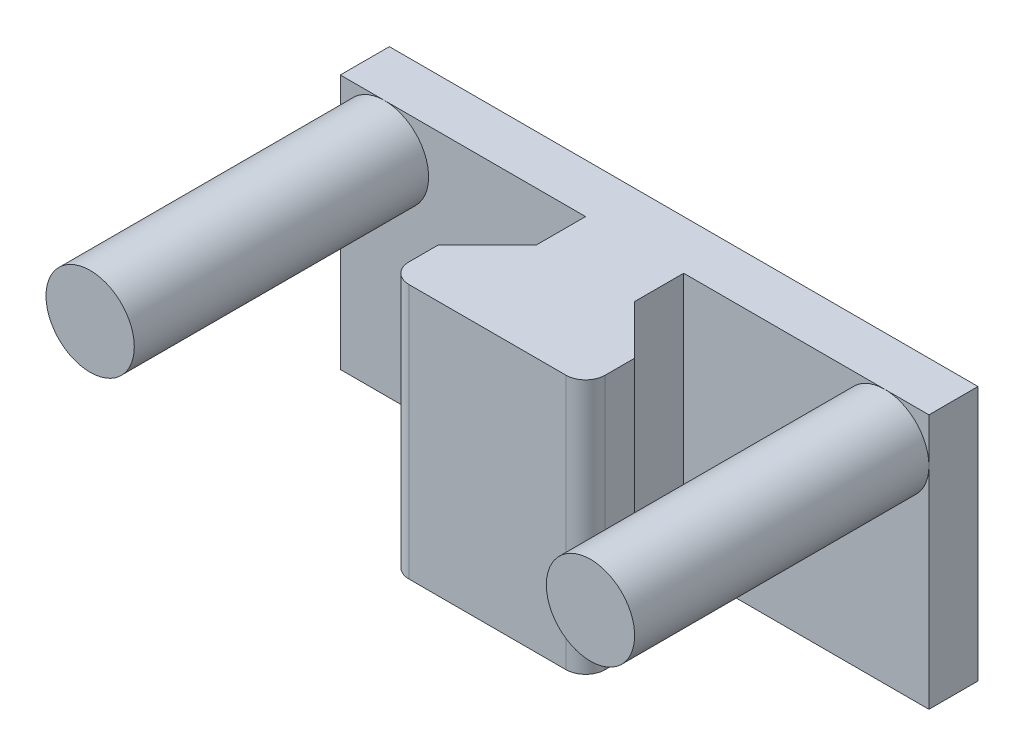
SolidWorks part; units mm, degrees
ref_plane "Front Plane" through (0, 0, 0) normal (0, 0, 1) x (1, 0, 0)
ref_plane "Top Plane" through (0, 0, 0) normal (0, 1, 0) x (1, 0, 0)
ref_plane "Right Plane" through (0, 0, 0) normal (1, 0, 0) x (0, 0, -1)
sketch "Sketch1" plane through (0, 0, 0) normal (0, 1, 0) x (1, 0, 0)
  line L0 (10, 0) -> (-10, 0)
  line L1 (-10, 0) -> (-10, 5)
  line L2 (-10, 5) -> (-5, 5)
  line L3 (-5, 5) -> (-5, 15)
  line L4 (-5, 15) -> (-30, 15)
  line L5 (-30, 15) -> (-30, 20)
  line L6 (-30, 20) -> (30, 20)
  line L7 (0, 20) -> (0, 0)
  line L8 (30, 15) -> (30, 20)
  line L9 (5, 15) -> (30, 15)
  line L10 (5, 5) -> (5, 15)
  line L11 (10, 5) -> (5, 5)
  line L12 (10, 0) -> (10, 5)
  dimension "D1" = 10
  dimension "D2" = 5
  dimension "D3" = 10
  dimension "D4" = 30
  dimension "D5" = 5
  dimension "D6" = 5
extrude "Boss-Extrude1" add sketch "Sketch1" along normal blind 26 contours L7 L6 L5 L4 L3 L2 L1 L0 | L0 L12 L11 L10 L9 L8 L6 L7 region at (5, 0, -0.3606) region at (-5, 0, -0.3606)
sketch "Sketch2" plane through (0, 0, -15) normal (0, 0, 1) x (1, 0, 0)
  line L1 (-5, 26) -> (-30, 26) construction
  line L2 (-30, 26) -> (-30, 0) construction
  circle A0 centre (-25.5, 21.5) radius 4.5
  dimension "D1" = 9
extrude "Boss-Extrude2" add sketch "Sketch2" along normal blind 30 contours A0
mirror "Mirror1" about plane through (0, 0, 0) normal (1, 0, 0) of "Boss-Extrude2"
fillet "Fillet1" radius 2 2 edges at (10, 13, 0) (-10, 13, 0)
chamfer "Chamfer1" distance 5 angle 45 2 edges at (5, 13, -5) (-5, 13, -5)
equation "\"shaftDiam\" = 20mm"
equation "\"keyW\" = 8mm"
equation "\"keyL\" = 10mm"
equation "\"clearance\" = 1mm"
equation "\"handleShaftLen\" = 60mm"
equation "\"panelH\" = 80mm"
equation "\"panelW\" = 110mm"
equation "\"D1@Sketch1\"=\"shaftDiam\"/2"
equation "\"D2@Sketch1\"=\"shaftDiam\"/4"
equation "\"D3@Sketch1\"=\"shaftDiam\"/2"
equation "\"D4@Sketch1\"= \"shaftDiam\" * 1.5"
equation "\"D5@Sketch1\"=\"shaftDiam\"/4"
equation "\"D6@Sketch1\"=\"shaftDiam\"/4"
equation "\"D1@Boss-Extrude1\"= \"shaftDiam\" + \"handleShaftLen\" / 10"
equation "\"D1@Sketch2\"= \"shaftDiam\" / 2 - \"clearance\""
equation "\"D1@Boss-Extrude2\"=\"shaftDiam\"*1.5"
equation "\"D1@Fillet1\"=\"shaftDiam\"/10"
equation "\"D1@Chamfer1\"= \"shaftDiam\" / 4"
